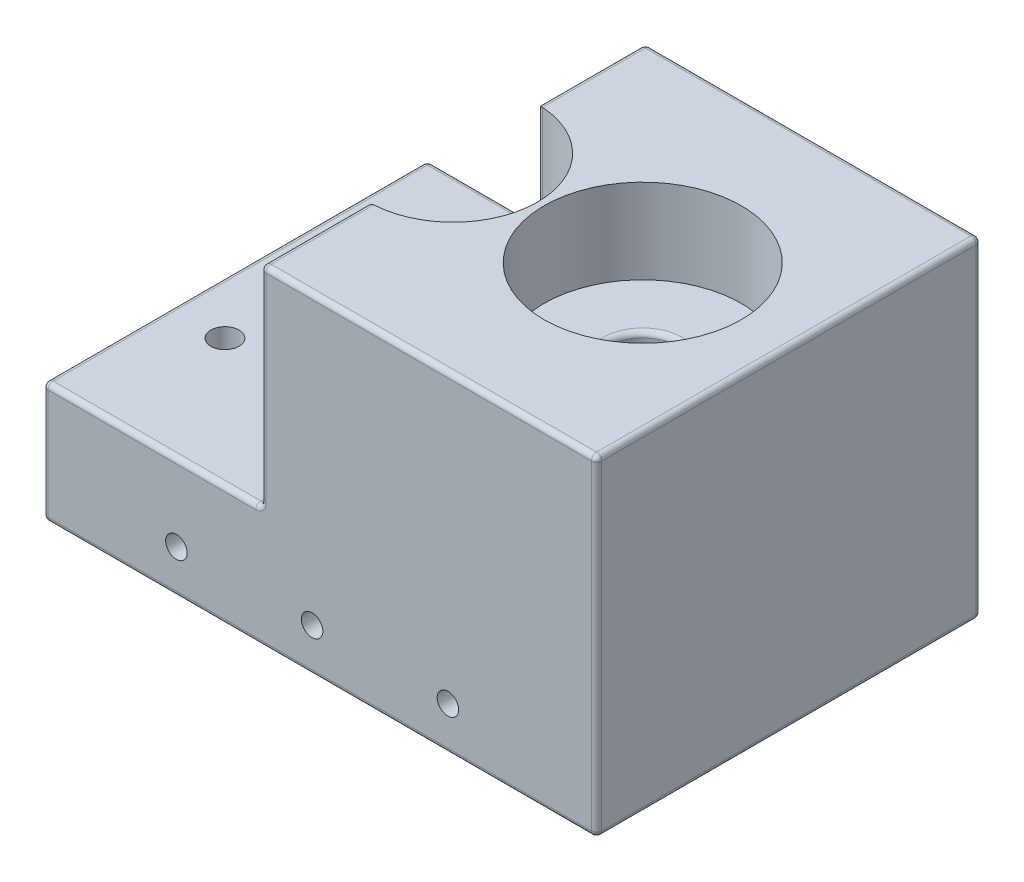
SolidWorks part; units mm, degrees
material "ABS"
ref_plane "Front Plane" through (0, 0, 0) normal (0, 0, 1) x (1, 0, 0)
ref_plane "Top Plane" through (0, 0, 0) normal (0, 1, 0) x (1, 0, 0)
ref_plane "Right Plane" through (0, 0, 0) normal (1, 0, 0) x (0, 0, -1)
sketch "Sketch1" plane through (0, 0, 0) normal (0, 1, 0) x (1, 0, 0)
  line L1 (-54, -37.5) -> (54, -37.5)
  line L2 (-54, -37.5) -> (-54, 37.5)
  line L3 (-54, 37.5) -> (54, 37.5)
  line L4 (54, -37.5) -> (54, 37.5)
  line L5 (-54, -37.5) -> (54, 37.5) construction
  line L6 (-54, 37.5) -> (54, -37.5) construction
  point P0 (0, 0)
  dimension "D1" = 75
  dimension "D2" = 108
extrude "Boss-Extrude1" add sketch "Sketch1" along normal blind 23.5 contours L3 L4 L1 L2
sketch "Sketch2" plane through (0, 23.5, 0) normal (0, 1, 0) x (1, 0, 0)
  line L0 (-33, 13.75) -> (-33, -13.75) construction
  line L1 (-11.5, 16.5) -> (-11.5, -16.5) construction
  line L2 (-33, 13.75) -> (-11.5, 16.5)
  line L3 (-11.5, -16.5) -> (-33, -13.75)
  line L4 (-33, -13.75) -> (-33, 13.75)
  line L5 (-54, -37.5) -> (-54, 37.5) construction
  arc A0 (-11.5, 16.5) -> (-11.5, -16.5) centre (-11.5, 0) cw
  point P5 (-11.5, 0)
  point P6 (-11.5, 0)
  dimension "D6" = 21
  dimension "D1" = 27.5
  dimension "D2" = 13.75
  dimension "D3" = 33
  dimension "D4" = 16.5
  dimension "D5" = 21.5
extrude "Cut-Extrude1" cut sketch "Sketch2" against normal blind 13
sketch "Sketch3" plane through (0, 10.5, 0) normal (0, 1, 0) x (1, 0, 0)
  line L0 (-33, 13.75) -> (-33, -13.75) construction
  circle A0 centre (-11.5, 0) radius 10
  point P0 (-11.5, 0)
  dimension "D2" = 20
  dimension "D1" = 21.5
extrude "Cut-Extrude2" cut sketch "Sketch3" against normal blind 20
sketch "Sketch4" plane through (0, 23.5, 0) normal (0, 1, 0) x (1, 0, 0)
  line L0 (-11.5, 16.5) -> (-11.5, 37.5)
  line L1 (-54, 37.5) -> (54, 37.5) construction
  line L2 (-11.5, 37.5) -> (54, 37.5)
  line L3 (54, 37.5) -> (54, -37.5)
  line L4 (54, -37.5) -> (-11.5, -37.5)
  line L5 (-54, -37.5) -> (54, -37.5) construction
  line L6 (-11.5, -37.5) -> (-11.5, -16.5)
  arc A0 (-11.5, -16.5) -> (-11.5, 16.5) centre (-11.5, 0) ccw construction
  circle A1 centre (27, 0) radius 6.5 construction
  circle A2 centre (27, 0) radius 19 construction
  arc A3 (-11.5, 16.5) -> (-11.5, -16.5) centre (-11.5, 0) cw
  arc A4 (-11.5, -16.5) -> (-11.5, 16.5) centre (-11.5, 0) ccw construction
  point P0 (27, 0)
  point P7 (-11.5, 0)
  dimension "D2" = 13
  dimension "D3" = 38
  dimension "D1" = 38.5
extrude "Boss-Extrude2" add sketch "Sketch4" along normal blind 41
sketch "Sketch5" plane through (0, 64.5, 0) normal (0, 1, 0) x (1, 0, 0)
  arc A0 (-11.5, -16.5) -> (-11.5, 16.5) centre (-11.5, 0) ccw construction
  circle A1 centre (25.5, 0) radius 19.25
  point P0 (25.5, 0)
  dimension "D2" = 38.5
  dimension "D1" = 37
extrude "Cut-Extrude3" cut sketch "Sketch5" against normal blind 16.5
sketch "Sketch6" plane through (0, 48, 0) normal (0, 1, 0) x (1, 0, 0)
  circle A0 centre (25.5, 0) radius 6.75
  point P0 (25.5, 0)
  dimension "D1" = 13.5
extrude "Cut-Extrude4" cut sketch "Sketch6" against normal blind 3.5
fillet "Fillet1" radius 2 1 edges at (-33, 17, -13.75)
fillet "Fillet2" radius 2 1 edges at (-33, 17, 13.75)
fillet "Fillet4" radius 1 1 edges at (25.5, 48, 6.75)
fillet "Fillet6" radius 1 5 edges at (-21.3769, 23.5, 15.2367) (-32.5012, 23.5, 13.311) (-33, 23.5, 0) (-32.5012, 23.5, -13.311) (-21.3769, 23.5, -15.2367)
fillet "Fillet10" radius 1 1 edges at (-11.5, 43.5, -16.5)
fillet "Fillet11" radius 1 4 edges at (-11.5, 23.4998, -17.4898) (-11.3059, 23.2613, -16.8793) (-10.9371, 16.5, -16.572)
fillet "Fillet15" radius 1 1 edges at (-11.5, 43.5, 16.5)
fillet "Fillet16" radius 1 4 edges at (-11.2137, 23.141, 16.771) (-10.9371, 16.5, 16.572) (-11.5, 23.4998, 17.4898)
fillet "Fillet18" radius 1 1 edges at (-11.5, 64.5, 27.4857) tangent propagation no
fillet "Fillet19" radius 1 1 edges at (-11.5, 64.5, -27.4857) tangent propagation no
fillet "Fillet20" radius 1 1 edges at (54, 64.5, 0)
fillet "Fillet21" radius 1 7 edges at (54, 31.75, -37.5) (53.7071, 64.2071, -37.5) (-11.7929, 23.7929, -37.5) (-11.2071, 64.2071, -37.5) (21.25, 64.5, -37.5)
fillet "Fillet22" radius 1 7 edges at (-11.7929, 23.7929, 37.5) (-11.2071, 64.2071, 37.5) (54, 31.75, 37.5) (53.7071, 64.2071, 37.5) (21.25, 64.5, 37.5)
fillet "Fillet23" radius 1 11 edges at (-0.5, 0, 37.5) (53.7071, 0, 37.2071) (54, 0, 0) (53.7071, 0, -37.2071) (-54, 11.25, 37.5) (-54, 23.2071, 37.2071) (-54, 11.25, -37.5) (-54, 23.2071, -37.2071) (-0.5, 0, -37.5) (-54, 0, 0) (-54, 23.5, 0)
fillet "Fillet24" radius 1 1 edges at (-11.5, 10.5, 10)
fillet "Fillet25" radius 1 1 edges at (-11.5, 0, -10)
sketch "Sketch7" plane through (0, 0, 37.5) normal (0, 0, 1) x (1, 0, 0)
  line L0 (-53, 8.5) -> (57.2263, 8.5) construction
  line L1 (-53, 22.5) -> (-53, 1) construction
  line L2 (-12.5, 22.5) -> (-53, 22.5) construction
  line L3 (53, 1) -> (53, 63.5) construction
  circle A0 centre (-27.97, 8.5) radius 2.1
  circle A1 centre (-1.5, 8.5) radius 2.1
  circle A2 centre (25, 8.5) radius 2.1
  point P6 (-27.97, 8.5)
  point P7 (-1.5, 8.5)
  point P8 (25, 8.5)
  dimension "D5" = 4.2
  dimension "D6" = 4.2
  dimension "D7" = 4.2
  dimension "D3" = 26.47
  dimension "D1" = 14
  dimension "D2" = 25.03
  dimension "D4" = 28
extrude "Cut-Extrude5" cut sketch "Sketch7" against normal blind 10
sketch "Sketch8" plane through (0, 0, -37.5) normal (0, 0, -1) x (-1, 0, 0)
  line L0 (-53, 8.5) -> (50.384, 8.5) construction
  line L1 (-53, 63.5) -> (-53, 1) construction
  line L2 (53, 22.5) -> (12.5, 22.5) construction
  line L3 (53, 1) -> (53, 22.5) construction
  circle A0 centre (-25.17, 8.5) radius 2.1
  circle A1 centre (1.58, 8.5) radius 2.1
  circle A2 centre (27.83, 8.5) radius 2.1
  point P6 (-25.17, 8.5)
  point P7 (1.58, 8.5)
  point P8 (27.83, 8.5)
  dimension "D5" = 4.2
  dimension "D6" = 4.2
  dimension "D7" = 4.2
  dimension "D1" = 14
  dimension "D2" = 27.83
  dimension "D3" = 51.42
  dimension "D4" = 25.17
extrude "Cut-Extrude6" cut sketch "Sketch8" against normal blind 10
sketch "Sketch9" plane through (0, 23.5, 0) normal (0, 1, 0) x (1, 0, 0)
  line L0 (-43.5, 37.5) -> (-43.5, -37.5) construction
  line L1 (-53, 37.5) -> (-12.5, 37.5) construction
  line L2 (-12.5, -37.5) -> (-53, -37.5) construction
  line L3 (-54, -36.5) -> (-54, 36.5) construction
  circle A0 centre (-43.5, 12.5) radius 2.75
  circle A1 centre (-43.5, -12.5) radius 2.75
  point P8 (-43.5, 12.5)
  point P9 (-43.5, -12.5)
  dimension "D4" = 5.5
  dimension "D5" = 5.5
  dimension "D1" = 10.5
  dimension "D2" = 25
  dimension "D3" = 25
extrude "Cut-Extrude7" cut sketch "Sketch9" against normal blind 25
sketch "Sketch10" plane through (0, 0, 0) normal (0, -1, 0) x (1, 0, 0)
  line L0 (-43.5, 36.5) -> (-43.5, -37.5) construction
  line L1 (53, 36.5) -> (-53, 36.5) construction
  line L2 (53, -37.5) -> (-53, -37.5) construction
  circle A0 centre (-43.5, 12.5) radius 5
  circle A1 centre (-43.5, -12.5) radius 5
  point P7 (-43.5, 12.5)
  point P8 (-43.5, -12.5)
  dimension "D1" = 10
  dimension "D2" = 10
extrude "Cut-Extrude8" cut sketch "Sketch10" against normal blind 8
sketch "Sketch11" plane through (0, 0, 0) normal (0, -1, 0) x (1, 0, 0)
  line L0 (-1.5, 0) -> (59.8836, 0) construction
  line L2 (53, -36.5) -> (53, 36.5) construction
  circle A0 centre (-11.5, 0) radius 10 construction
  circle A1 centre (49.5, 0) radius 3.55
  point P6 (49.5, 0)
  dimension "D2" = 7.1
  dimension "D1" = 3.5
extrude "Cut-Extrude9" cut sketch "Sketch11" against normal blind 10 contours A1
